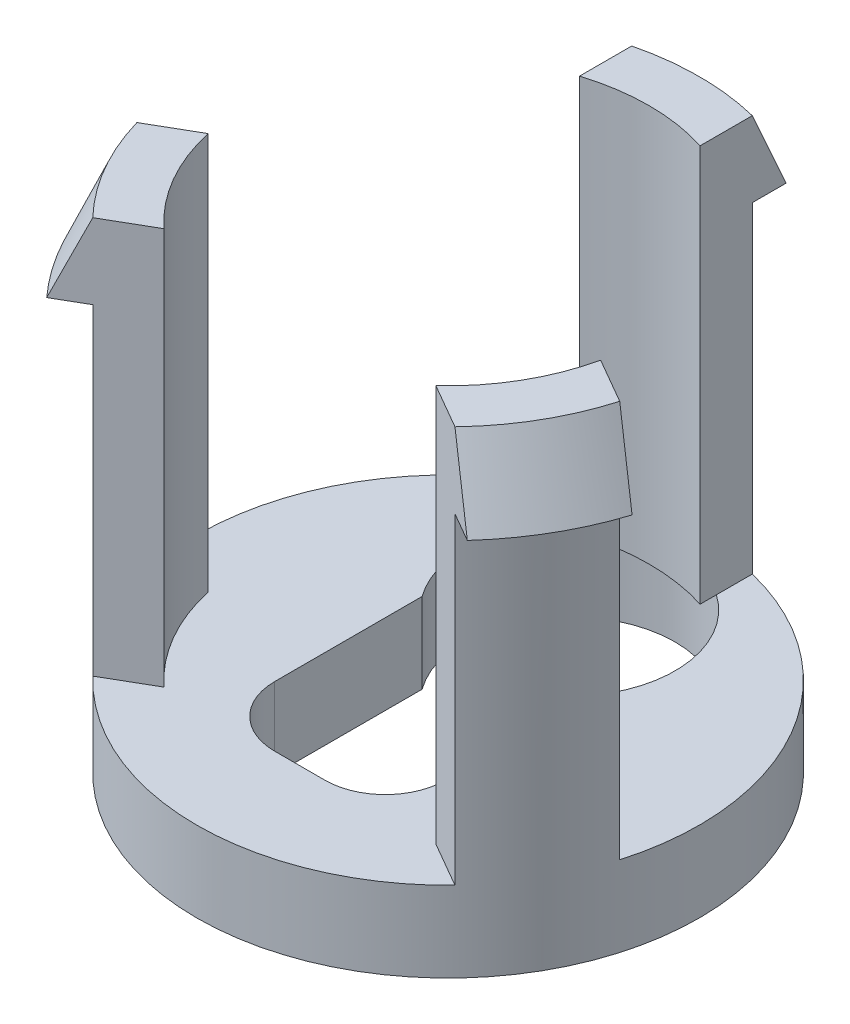
SolidWorks part; units mm, degrees
ref_plane "Front Plane" through (0, 0, 0) normal (0, 0, 1) x (1, 0, 0)
ref_plane "Top Plane" through (0, 0, 0) normal (0, 1, 0) x (1, 0, 0)
ref_plane "Right Plane" through (0, 0, 0) normal (1, 0, 0) x (0, 0, -1)
sketch "Sketch1" plane through (0, 0, 0) normal (0, 1, 0) x (1, 0, 0)
  circle A0 centre (0, 0) radius 5
  circle A1 centre (0, 0) radius 3.8 construction
  dimension "D1" = 10
  dimension "D2" = 1.2
extrude "Boss-Extrude1" add sketch "Sketch1" along normal blind 1.6
sketch "Sketch2" plane through (0, 1.6, 0) normal (0, 1, 0) x (1, 0, 0)
  line L2 (-1.2, 4.8539) -> (-1.2, 3.8158)
  line L4 (1.2, 4.8539) -> (1.2, 3.8158)
  circle A0 centre (0, 0) radius 5 construction
  arc A1 (1.2, 4.8539) -> (-1.2, 4.8539) centre (0, 0) ccw
  arc A2 (1.2, 3.8158) -> (-1.2, 3.8158) centre (0, 0) ccw
  circle A3 centre (0, 0) radius 5 construction
  circle A4 centre (0, 0) radius 4 construction
  dimension "D2" = 1.2
  dimension "D3" = 1.2
  dimension "D1" = 1
extrude "Boss-Extrude2" add sketch "Sketch2" along normal blind 7.9
pattern_circular "CirPattern3" count 3 over 360 about axis through (0, 1.6, 0) along (0, -1, 0) of "Boss-Extrude2"
sketch "Sketch3" plane through (0, 0, 0) normal (1, 0, 0) x (0, 0, -1)
  line L0 (5, 9.5) -> (5.6539, 8)
  line L1 (5, 9.5) -> (4.8539, 9.5) construction
  line L2 (5.6539, 8) -> (4.8539, 8)
  line L4 (4.8539, 9.5) -> (4.8539, 1.6) construction
  line L5 (4.8539, 8) -> (4.8539, 9.5)
  line L6 (4.8539, 9.5) -> (5, 9.5)
  dimension "D1" = 1.5
  dimension "D2" = 0.8
sketch "Sketch6" plane through (0, 9.5, 0) normal (0, 1, 0) x (1, 0, 0)
  circle A0 centre (0, 0) radius 5
sweep "Sweep3" add profiles "Sketch3" path "Sketch6"
sketch "Sketch7" plane through (0, 1.6, 0) normal (0, 1, 0) x (1, 0, 0)
  line L0 (-3.9045, -0.8686) -> (-4.8036, -1.3877) construction
  line L1 (-3.9045, -0.8686) -> (-4.8036, -1.3877)
  line L2 (-1.2, 4.8539) -> (-1.2, 3.8158) construction
  line L3 (1.2, 3.8158) -> (1.2, 4.8539) construction
  line L4 (4.8036, -1.3877) -> (3.9045, -0.8686) construction
  line L5 (2.7045, -2.9471) -> (3.6036, -3.4662) construction
  line L6 (-3.6036, -3.4662) -> (-2.7045, -2.9471) construction
  line L7 (-1.2, 4.8539) -> (-1.2, 3.8158)
  line L8 (1.2, 3.8158) -> (1.2, 4.8539)
  line L9 (4.8036, -1.3877) -> (3.9045, -0.8686)
  line L10 (2.7045, -2.9471) -> (3.6036, -3.4662)
  line L11 (-3.6036, -3.4662) -> (-2.7045, -2.9471)
  arc A0 (-1.2, 4.8539) -> (-4.8036, -1.3877) centre (0, 0) ccw construction
  arc A1 (-1.2, 4.8539) -> (-4.8036, -1.3877) centre (0, 0) ccw
  arc A2 (4.8036, -1.3877) -> (1.2, 4.8539) centre (0, 0) ccw construction
  arc A3 (1.2, 3.8158) -> (-1.2, 3.8158) centre (0, 0) ccw construction
  arc A4 (-3.6036, -3.4662) -> (3.6036, -3.4662) centre (0, 0) ccw construction
  arc A5 (-3.9045, -0.8686) -> (-2.7045, -2.9471) centre (0, 0) ccw construction
  arc A6 (2.7045, -2.9471) -> (3.9045, -0.8686) centre (0, 0) ccw construction
  arc A7 (4.8036, -1.3877) -> (1.2, 4.8539) centre (0, 0) ccw
  arc A8 (1.2, 3.8158) -> (-1.2, 3.8158) centre (0, 0) ccw
  arc A9 (-3.6036, -3.4662) -> (3.6036, -3.4662) centre (0, 0) ccw
  arc A10 (-3.9045, -0.8686) -> (-2.7045, -2.9471) centre (0, 0) ccw
  arc A11 (2.7045, -2.9471) -> (3.9045, -0.8686) centre (0, 0) ccw
extrude "Cut-Extrude2" cut sketch "Sketch7" along normal through all
sketch "Sketch8" plane through (0, 8, 0) normal (0, -1, 0) x (1, 0, 0)
  line L0 (-3.6036, 3.4662) -> (-2.7045, 2.9471) construction
  line L1 (-3.6036, 3.4662) -> (-4.1848, 3.8018)
  line L2 (-3.9045, 0.8686) -> (-4.8036, 1.3877) construction
  line L3 (-1.2, -4.8539) -> (-1.2, -3.8158) construction
  line L4 (1.2, -3.8158) -> (1.2, -4.8539) construction
  line L5 (4.8036, 1.3877) -> (3.9045, 0.8686) construction
  line L6 (2.7045, 2.9471) -> (3.6036, 3.4662) construction
  line L7 (-5.3848, 1.7233) -> (-4.8036, 1.3877)
  line L8 (-1.2, -4.8539) -> (-1.2, -5.5251)
  line L9 (1.2, -5.5251) -> (1.2, -4.8539)
  line L10 (4.8036, 1.3877) -> (5.3848, 1.7233)
  line L11 (4.1848, 3.8018) -> (3.6036, 3.4662)
  circle A0 centre (0, 0) radius 5.6539 construction
  arc A1 (-5.3848, 1.7233) -> (-1.2, -5.5251) centre (0, 0) ccw
  arc A2 (3.6036, 3.4662) -> (-3.6036, 3.4662) centre (0, 0) ccw construction
  arc A3 (-4.8036, 1.3877) -> (-1.2, -4.8539) centre (0, 0) ccw
  arc A4 (1.2, -5.5251) -> (5.3848, 1.7233) centre (0, 0) ccw
  arc A5 (1.2, -4.8539) -> (4.8036, 1.3877) centre (0, 0) ccw
  arc A6 (3.6036, 3.4662) -> (-3.6036, 3.4662) centre (0, 0) ccw
  arc A7 (4.1848, 3.8018) -> (-4.1848, 3.8018) centre (0, 0) ccw
extrude "Cut-Extrude3" cut sketch "Sketch8" against normal through all
sketch "Sketch9" plane through (0, 1.6, 0) normal (0, 1, 0) x (1, 0, 0)
  line L0 (-1.5, 1.25) -> (-1.5, -1.75) construction
  line L1 (1.5, -1.75) -> (1.5, 1.25) construction
  line L2 (-0.5, -2.75) -> (0.5, -2.75) construction
  line L3 (-1.5, 1.25) -> (-1.5, -1.75) construction
  line L4 (1.5, -1.75) -> (1.5, 1.25) construction
  line L5 (-0.5, -2.75) -> (0.5, -2.75) construction
  line L6 (-1.7, 1.1833) -> (-1.7, -1.75)
  line L7 (-0.5, -2.95) -> (0.5, -2.95)
  line L8 (1.7, -1.75) -> (1.7, 1.1833)
  arc A1 (0.5, -2.75) -> (1.5, -1.75) centre (0.5, -1.75) ccw construction
  arc A2 (-1.5, -1.75) -> (-0.5, -2.75) centre (-0.5, -1.75) ccw construction
  arc A3 (1.5, 1.25) -> (-1.5, 1.25) centre (0, 2.4162) ccw construction
  arc A4 (0.5, -2.75) -> (1.5, -1.75) centre (0.5, -1.75) ccw construction
  arc A5 (-1.5, -1.75) -> (-0.5, -2.75) centre (-0.5, -1.75) ccw construction
  arc A6 (-1.7, -1.75) -> (-0.5, -2.95) centre (-0.5, -1.75) ccw
  arc A7 (0.5, -2.95) -> (1.7, -1.75) centre (0.5, -1.75) ccw
  arc A8 (1.7, 1.1833) -> (-1.7, 1.1833) centre (0, 2.4162) ccw
  dimension "D1" = 0.2
extrude "Cut-Extrude4" cut sketch "Sketch9" against normal through all
